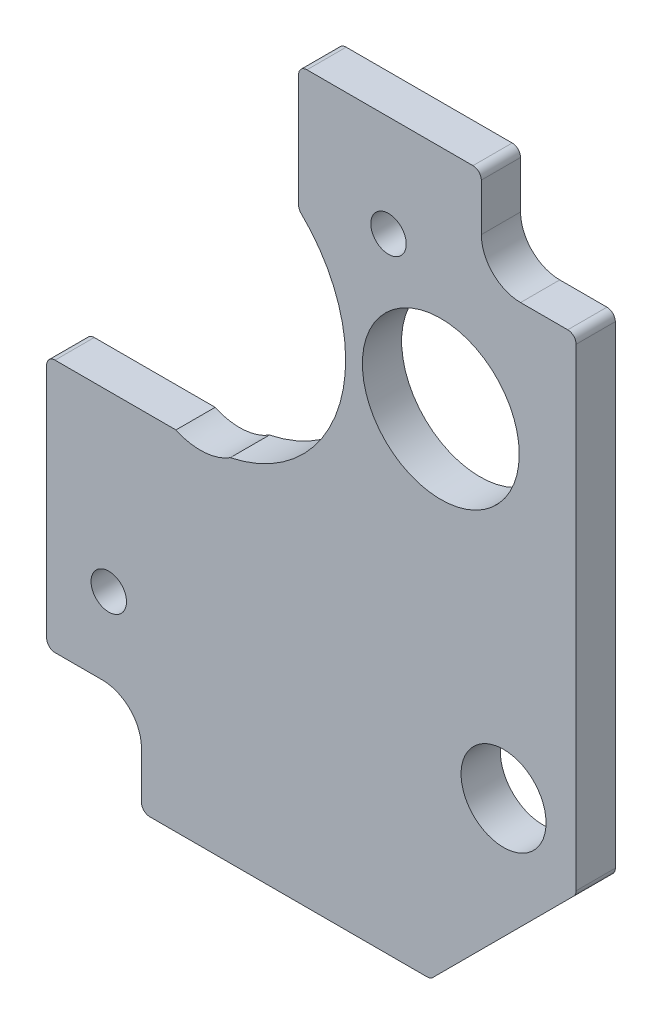
SolidWorks part; units mm, degrees
material "Acrylic (Medium-high impact)"
ref_plane "Front Plane" through (0, 0, 0) normal (0, 0, 1) x (1, 0, 0)
ref_plane "Top Plane" through (0, 0, 0) normal (0, 1, 0) x (1, 0, 0)
ref_plane "Right Plane" through (0, 0, 0) normal (1, 0, 0) x (0, 0, -1)
sketch "Sketch1" plane through (0, 0, 0) normal (0, 0, 1) x (1, 0, 0)
  line L11 (-17.784, -88.2055) -> (-0.6945, -71.116)
  line L12 (-0.3969, -70.3975) -> (-0.3969, -12.9223)
  line L13 (-1.4129, -11.9063) -> (-7.1438, -11.9063)
  line L14 (-11.9063, -7.1438) -> (-11.9063, -1.4129)
  line L15 (-12.9223, -0.3969) -> (-33.0835, -0.3969)
  line L16 (-34.0995, -1.4129) -> (-34.0995, -15.1316)
  line L17 (-48.991, -46.228) -> (-63.6746, -46.228)
  line L18 (-64.6906, -47.244) -> (-64.6906, -75.9778)
  line L19 (-63.6746, -76.9938) -> (-57.9438, -76.9938)
  line L20 (-53.1813, -81.7563) -> (-53.1813, -87.4871)
  line L21 (-52.1653, -88.5031) -> (-18.5025, -88.5031)
  line L22 (-17.784, -88.2055) -> (-0.6945, -71.116)
  line L23 (-0.3969, -70.3975) -> (-0.3969, -12.9223)
  line L24 (-1.4129, -11.9063) -> (-7.1438, -11.9063)
  line L25 (-11.9063, -7.1438) -> (-11.9063, -1.4129)
  line L26 (-12.9223, -0.3969) -> (-33.0835, -0.3969)
  line L27 (-34.0995, -1.4129) -> (-34.0995, -15.1316)
  line L28 (-48.991, -46.228) -> (-63.6746, -46.228)
  line L29 (-64.6906, -47.244) -> (-64.6906, -75.9778)
  line L30 (-63.6746, -76.9938) -> (-57.9438, -76.9938)
  line L31 (-53.1813, -81.7563) -> (-53.1813, -87.4871)
  line L32 (-52.1653, -88.5031) -> (-18.5025, -88.5031)
  arc A12 (-18.5025, -88.5031) -> (-17.784, -88.2055) centre (-18.5025, -87.4871) ccw
  arc A13 (-0.6945, -71.116) -> (-0.3969, -70.3975) centre (-1.4129, -70.3975) ccw
  arc A14 (-0.3969, -12.9223) -> (-1.4129, -11.9063) centre (-1.4129, -12.9223) ccw
  arc A15 (-11.9063, -7.1438) -> (-7.1438, -11.9063) centre (-7.1438, -7.1438) ccw
  arc A16 (-11.9063, -1.4129) -> (-12.9223, -0.3969) centre (-12.9223, -1.4129) ccw
  arc A17 (-33.0835, -0.3969) -> (-34.0995, -1.4129) centre (-33.0835, -1.4129) ccw
  arc A18 (-34.0995, -15.1316) -> (-33.7885, -15.8632) centre (-33.0835, -15.1316) ccw
  arc A19 (-42.3979, -45.8487) -> (-33.7885, -15.8632) centre (-46.0375, -28.575) ccw
  arc A20 (-63.6746, -46.228) -> (-64.6906, -47.244) centre (-63.6746, -47.244) ccw
  arc A21 (-64.6906, -75.9778) -> (-63.6746, -76.9938) centre (-63.6746, -75.9778) ccw
  arc A22 (-53.1813, -81.7563) -> (-57.9438, -76.9938) centre (-57.9438, -81.7563) ccw
  arc A23 (-53.1813, -87.4871) -> (-52.1653, -88.5031) centre (-52.1653, -87.4871) ccw
  arc A24 (-18.5025, -88.5031) -> (-17.784, -88.2055) centre (-18.5025, -87.4871) ccw
  arc A25 (-0.6945, -71.116) -> (-0.3969, -70.3975) centre (-1.4129, -70.3975) ccw
  arc A26 (-0.3969, -12.9223) -> (-1.4129, -11.9063) centre (-1.4129, -12.9223) ccw
  arc A27 (-11.9063, -7.1438) -> (-7.1438, -11.9063) centre (-7.1438, -7.1438) ccw
  arc A28 (-11.9063, -1.4129) -> (-12.9223, -0.3969) centre (-12.9223, -1.4129) ccw
  arc A29 (-33.0835, -0.3969) -> (-34.0995, -1.4129) centre (-33.0835, -1.4129) ccw
  arc A30 (-34.0995, -15.1316) -> (-33.7885, -15.8632) centre (-33.0835, -15.1316) ccw
  arc A31 (-42.3979, -45.8487) -> (-33.7885, -15.8632) centre (-46.0375, -28.575) ccw
  arc A32 (-63.6746, -46.228) -> (-64.6906, -47.244) centre (-63.6746, -47.244) ccw
  arc A33 (-64.6906, -75.9778) -> (-63.6746, -76.9938) centre (-63.6746, -75.9778) ccw
  arc A34 (-53.1813, -81.7563) -> (-57.9438, -76.9938) centre (-57.9438, -81.7563) ccw
  arc A35 (-53.1813, -87.4871) -> (-52.1653, -88.5031) centre (-52.1653, -87.4871) ccw
  spline S1 degree 2 poles (-42.3979, -45.8487) (-45.5518, -47.8608) (-48.991, -46.228) knots -2.210611 -2.210611 -2.210611 -1.065002 -1.065002 -1.065002 weights 1 0.840384 1
  spline S2 degree 2 poles (-42.3979, -45.8487) (-45.5518, -47.8608) (-48.991, -46.228) knots -2.210611 -2.210611 -2.210611 -1.065002 -1.065002 -1.065002 weights 1 0.840384 1
  dimension "D1" = 0
extrude "Boss-Extrude1" add sketch "Sketch1" along normal blind 4.7625
hole_wizard "#6 Clearance Hole1" positions "Sketch3" profile "Sketch2" hole size "#6" standard "ANSI Inch" end condition through all
sketch "Sketch3" plane through (0, 0, 4.7625) normal (0, 0, 1) x (1, 0, 0)
  point P0 (-57.15, -67.31)
  point P3 (-23.1775, -12.7)
sketch "Sketch2" plane through (-57.15, -67.31, 4.7625) normal (1, 0, 0) x (0, -1, 0)
  line L0 (0, 0) -> (0, 4.7625)
  line L1 (0, 4.7625) -> (2.1526, 4.7625)
  line L2 (2.1526, 4.7625) -> (2.1526, 0)
  line L5 (2.1526, 0) -> (0, 0)
  line L11 (0, -6.35) -> (0, 107.95) construction
  dimension "Thru Hole Dia." = 4.3053
  dimension "Thru Hole Depth" = 4.7625
hole_wizard "3/4 (0.75) Diameter Hole1" positions "Sketch6" profile "Sketch4" hole size "3/4" standard "ANSI Inch" end condition through all
sketch "Sketch6" plane through (0, 0, 4.7625) normal (0, 0, 1) x (1, 0, 0)
  point P0 (-16.8275, -27.94)
sketch "Sketch4" plane through (-16.8275, -27.94, 4.7625) normal (1, 0, 0) x (0, -1, 0)
  line L0 (0, 0) -> (0, 4.7625)
  line L1 (0, 4.7625) -> (9.525, 4.7625)
  line L2 (9.525, 4.7625) -> (9.525, 0)
  line L5 (9.525, 0) -> (0, 0)
  line L11 (0, -6.35) -> (0, 107.95) construction
  dimension "Thru Hole Dia." = 19.05
  dimension "Thru Hole Depth" = 4.7625
hole_wizard "13/32 (0.40625) Diameter Hole1" positions "Sketch8" profile "Sketch7" hole size "13/32" standard "ANSI Inch" end condition through all
sketch "Sketch8" plane through (0, 0, 4.7625) normal (0, 0, 1) x (1, 0, 0)
  point P0 (-9.2075, -65.0875)
sketch "Sketch7" plane through (-9.2075, -65.0875, 4.7625) normal (1, 0, 0) x (0, -1, 0)
  line L0 (0, 0) -> (0, 4.7625)
  line L1 (0, 4.7625) -> (5.1594, 4.7625)
  line L2 (5.1594, 4.7625) -> (5.1594, 0)
  line L5 (5.1594, 0) -> (0, 0)
  line L11 (0, -6.35) -> (0, 107.95) construction
  dimension "Thru Hole Dia." = 10.3187
  dimension "Thru Hole Depth" = 4.7625
